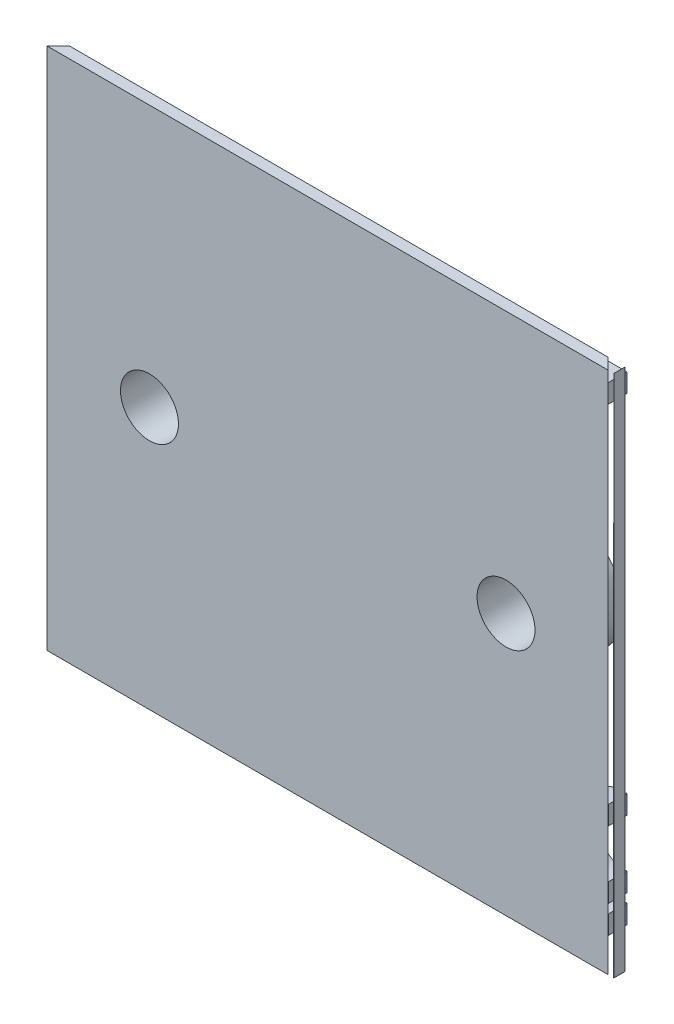
SolidWorks part; units mm, degrees
ref_plane "Спереди" through (0, 0, 0) normal (0, 0, 1) x (1, 0, 0)
ref_plane "Сверху" through (0, 0, 0) normal (0, 1, 0) x (1, 0, 0)
ref_plane "Справа" through (0, 0, 0) normal (1, 0, 0) x (0, 0, -1)
other "Configuration Table"
sketch "Эскиз1" plane through (0, 0, 0) normal (0, 0, 1) x (1, 0, 0)
  line L0 (-36, -28.0142) -> (36, -28.0142)
  line L1 (30.6, -28.0142) -> (30.6, 27.9858)
  line L2 (-30.6072, 28.0142) -> (-30.5887, -27.9858)
  line L3 (36, 27.9858) -> (-36, 27.9858)
  line L4 (34.9934, 26.0358) -> (-35.0066, 26.0127)
  line L5 (-34.9894, -25.9873) -> (35.0106, -25.9642)
  circle A0 centre (-28.5, -18.0142) radius 2
  circle A1 centre (28.5, -18.0142) radius 2
  circle A2 centre (-19.068, 0.018) radius 2.6
  circle A3 centre (19.07, -0.0142) radius 2.6
sketch "Эскиз3" plane through (0, 0, 0) normal (0, 0, 1) x (1, 0, 0)
  line L0 (30.6, -28.0142) -> (30.6, 27.9858) construction
  line L1 (-30.6072, 28.0142) -> (-30.5887, -27.9858) construction
  line L2 (30.6, -28.0142) -> (30.6, 27.9858)
  line L3 (-30.6072, 28.0142) -> (-30.5887, -27.9858)
  line L4 (-30.6072, 28.0142) -> (30.6, 27.9858)
  line L5 (-30.5887, -27.9858) -> (30.6, -28.0142)
  circle A0 centre (-19.068, 0.018) radius 2.6 construction
  circle A1 centre (19.07, -0.0142) radius 2.6 construction
  circle A2 centre (-19.068, 0.018) radius 2.6
  circle A3 centre (19.07, -0.0142) radius 2.6
extrude "Бобышка-Вытянуть1" add sketch "Эскиз3" along normal blind 1.2
sketch "Эскиз5" plane through (0, 0, 0) normal (0, 0, -1) x (-1, 0, 0)
  line L0 (-30.6, -28.0142) -> (-30.6, 27.9858) construction
  line L1 (-30.6, 26.0344) -> (30.6066, 26.0142)
  line L2 (-34.9934, 26.0358) -> (35.0066, 26.0127) construction
  line L3 (30.6072, 28.0142) -> (30.5887, -27.9858) construction
  line L4 (30.6066, 26.0142) -> (30.5894, -25.9858)
  line L5 (34.9894, -25.9873) -> (-35.0106, -25.9642) construction
  line L6 (30.5894, -25.9858) -> (-30.6, -25.9656)
  line L7 (-30.6, -25.9656) -> (-30.6, 26.0344)
extrude "Вытянуть-Тонкостенный1" add sketch "Эскиз5" along normal blind 2 thin thin type one direction reverse wall 2.4
sketch "Эскиз6" plane through (0, 0, -2) normal (0, 0, -1) x (-1, 0, 0)
  line L4 (-30.6, 26.0344) -> (-30.6, -25.9656)
  line L5 (-30.6, -25.9656) -> (30.5894, -25.9858)
  line L6 (30.5894, -25.9858) -> (30.6066, 26.0142)
  line L7 (30.6066, 26.0142) -> (-30.6, 26.0344)
  line L8 (-30.6, 26.0344) -> (-30.6, -25.9656)
  line L9 (-30.6, -25.9656) -> (30.5894, -25.9858)
  line L10 (30.5894, -25.9858) -> (30.6066, 26.0142)
  line L11 (30.6066, 26.0142) -> (-30.6, 26.0344)
  dimension "D1" = 0
extrude "Вырез-Вытянуть-Тонкостенный2" cut sketch "Эскиз6" against normal blind 2 thin thin type one direction reverse wall 0.4
sketch "Эскиз7" plane through (0, 0, -2) normal (0, 0, -1) x (-1, 0, 0)
  line L0 (-30.6, -28.0142) -> (-30.6, 27.9858) construction
  line L1 (-30.6, 23.6243) -> (30.5902, 23.6243)
  line L2 (-30.6, 23.6243) -> (-30.6, -23.5757)
  line L3 (-30.6, -23.5757) -> (30.5902, -23.5757)
  line L4 (30.5902, 23.6243) -> (30.5902, -23.5757)
  line L5 (30.6072, 28.0142) -> (30.5887, -27.9858) construction
extrude "Вырез-Вытянуть1" cut sketch "Эскиз7" against normal blind 2
sketch "Эскиз8" plane through (0, 0, 0) normal (0, 0, -1) x (-1, 0, 0)
  circle A0 centre (-19.07, -0.0142) radius 6
  circle A1 centre (19.068, 0.018) radius 6
  circle A2 centre (19.068, 0.018) radius 2.6 construction
  circle A3 centre (-19.07, -0.0142) radius 2.6 construction
  circle A4 centre (19.068, 0.018) radius 2.6
  circle A5 centre (-19.07, -0.0142) radius 2.6
  dimension "D1" = 12
  dimension "D2" = 12
extrude "Бобышка-Вытянуть2" add sketch "Эскиз8" along normal blind 5.4
sketch "Эскиз9" plane through (0, 0, -5.4) normal (0, 0, -1) x (-1, 0, 0)
  circle A0 centre (-19.07, -0.0142) radius 2
  circle A1 centre (19.068, 0.018) radius 2
  dimension "D1" = 4
  dimension "D2" = 4
extrude "Вытянуть-Тонкостенный2" add sketch "Эскиз9" against normal blind 2 thin thin type one direction wall 1
sketch "Эскиз10" plane through (0, 0, 0) normal (0, 0, -1) x (-1, 0, 0)
  circle A0 centre (28.5, -18.0142) radius 2 construction
  circle A1 centre (-28.5, -18.0142) radius 2 construction
  circle A2 centre (28.5, -18.0142) radius 2
  circle A3 centre (-28.5, -18.0142) radius 2
extrude "Вытянуть-Тонкостенный3" add sketch "Эскиз10" along normal blind 2 thin thin type one direction wall 2.6
sketch "Эскиз11" plane through (0, 0, -2) normal (0, 0, -1) x (-1, 0, 0)
  circle A0 centre (28.5, -18.0142) radius 2 construction
  circle A1 centre (-28.5, -18.0142) radius 2 construction
  circle A2 centre (28.5, -18.0142) radius 2
  circle A3 centre (-28.5, -18.0142) radius 2
extrude "Вырез-Вытянуть-Тонкостенный3" cut sketch "Эскиз11" against normal blind 2 thin thin type one direction wall 0.6
sketch "Эскиз12" plane through (0.013, 28, 0) normal (0.0005, 1, 0) x (1, -0.0005, 0)
  line L0 (29.987, -1.2) -> (28.787, 0)
  line L1 (30.587, -1.2) -> (-30.6202, -1.2) construction
  line L2 (-34.9774, 0) -> (35.0226, 0) construction
  line L3 (28.787, 0) -> (30.587, 0)
  line L4 (30.587, 0) -> (30.587, -1.2)
  line L5 (30.587, -1.2) -> (29.987, -1.2)
  line L6 (-30.0202, -1.2) -> (-28.8202, 0)
  line L7 (-30.0202, -1.2) -> (-30.6202, -1.2)
  line L8 (-30.6202, -1.2) -> (-30.6202, 0)
  line L9 (-30.6202, 0) -> (-28.8202, 0)
  dimension "D1" = 45
  dimension "D2" = 0.6
  dimension "D3" = 45
  dimension "D4" = 0.6
extrude "Вырез-Вытянуть4" cut sketch "Эскиз12" against normal blind 62
sketch "Эскиз13" plane through (-0.0085, 25.6243, 0) normal (-0.0003, 1, 0) x (1, 0.0003, 0)
  line L1 (-28.8308, 0) -> (-33.1059, 0)
  line L2 (-28.8308, 0) -> (-28.8308, 2)
  line L3 (-28.8308, 2) -> (-33.1059, 2)
  line L4 (-33.1059, 0) -> (-33.1059, 2)
  line L5 (28.8092, 0) -> (33.094, 0)
  line L6 (28.8092, 0) -> (28.8092, 2)
  line L7 (28.8092, 2) -> (33.094, 2)
  line L8 (33.094, 0) -> (33.094, 2)
extrude "Вырез-Вытянуть5" cut sketch "Эскиз13" against normal blind 62
sketch "Эскиз14" plane through (0, 0, -5.4) normal (0, 0, -1) x (-1, 0, 0)
  line L0 (28.8393, 25.6147) -> (-28.8008, 25.6338) construction
  line L5 (-15.47, 25.6294) -> (15.468, 25.6294)
  line L6 (-15.47, 25.6294) -> (-15.47, -25.5808)
  line L7 (-15.47, -25.5808) -> (15.468, -25.5808)
  line L8 (15.468, 25.6294) -> (15.468, -25.5808)
  line L9 (-28.8177, -25.5662) -> (28.8224, -25.5853) construction
  circle A3 centre (-19.07, -0.0142) radius 2 construction
  circle A4 centre (19.068, 0.018) radius 6 construction
  dimension "D1" = 3.6
  dimension "D2" = 3.6
extrude "Вырез-Вытянуть6" cut sketch "Эскиз14" against normal blind 5.4
sketch "Эскиз17" plane through (0, 0, 1.2) normal (0, 0, 1) x (1, 0, 0)
  circle A0 centre (-19.068, 0.018) radius 3.1
  circle A1 centre (19.07, -0.0142) radius 3.1
  dimension "D1" = 6.2
  dimension "D2" = 6.2
extrude "Вырез-Вытянуть8" cut sketch "Эскиз17" against normal blind 4.6
chamfer "Фаска1" distance 1.1 angle 45 2 edges at (-21.068, 0.018, -3.4) (17.07, -0.0142, -3.4)
